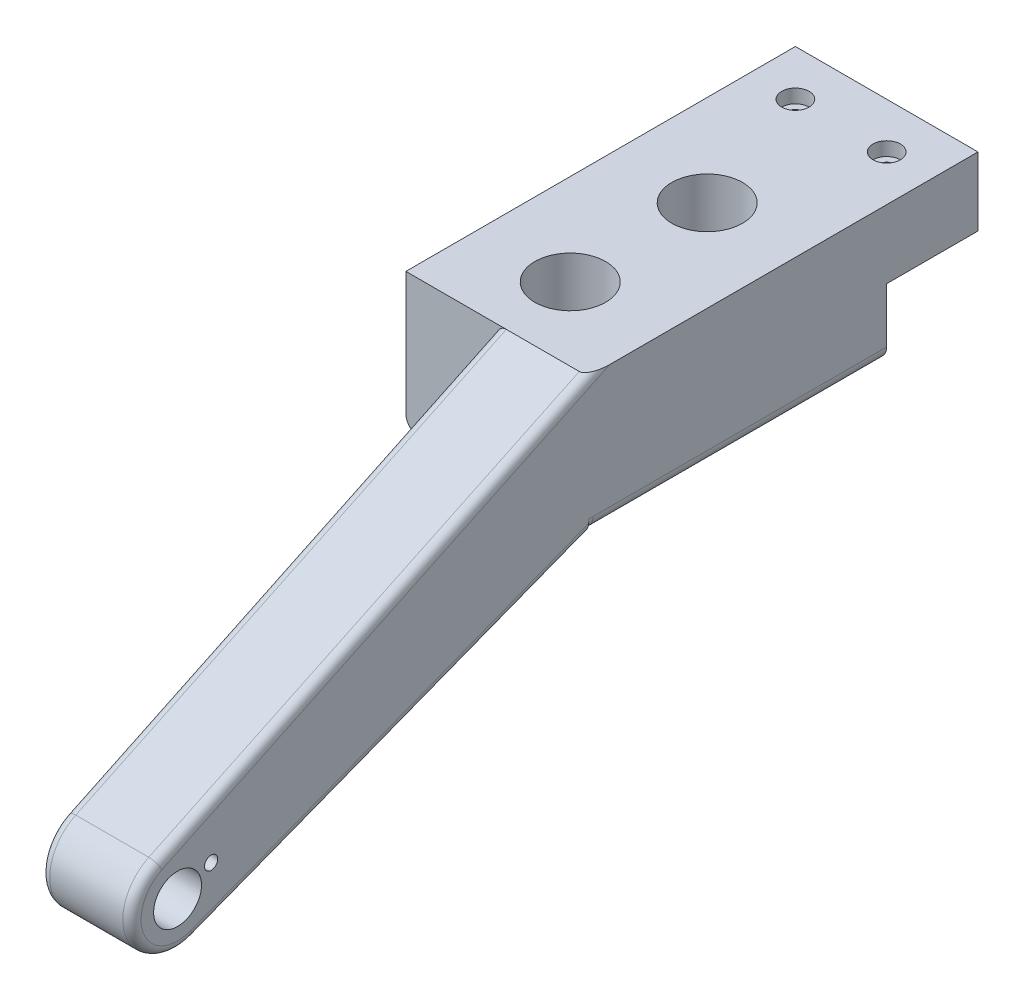
SolidWorks part; units mm, degrees
ref_plane "Front Plane" through (0, 0, 0) normal (0, 0, 1) x (1, 0, 0)
ref_plane "Top Plane" through (0, 0, 0) normal (0, 1, 0) x (1, 0, 0)
ref_plane "Right Plane" through (0, 0, 0) normal (1, 0, 0) x (0, 0, -1)
sketch "Sketch1" plane through (0, 0, 0) normal (0, 1, 0) x (1, 0, 0)
  line L1 (-20, 75) -> (20, 75)
  line L3 (-20, -75) -> (20, -75)
  line L4 (20, -75) -> (20, 75)
  line L5 (-20, -75) -> (-20, 75)
  circle A0 centre (0, -61.1649) radius 7.5
  circle A1 centre (0, -31.1649) radius 7.5
extrude "Boss-Extrude1" add sketch "Sketch1" against normal blind 30 contours L5 L1 L4 L3
sketch "Sketch3" plane through (0, 0, 0) normal (0, 1, 0) x (1, 0, 0)
  circle A0 centre (0, -60) radius 7.5
  circle A1 centre (0, -30) radius 7.5
extrude "Cut-Extrude1" cut sketch "Sketch3" against normal blind 30 contours A0 | A1
sketch "Sketch4" plane through (-20, 0, 0) normal (-1, 0, 0) x (0, 0, 1)
  line L1 (-75, -30) -> (-75, 0) construction
  line L2 (-75, -8) -> (0, -30)
  line L3 (75, -30) -> (-75, -30) construction
  line L4 (0, -30) -> (-75, -30)
  line L5 (-75, -30) -> (-75, -8)
extrude "Cut-Extrude2" cut sketch "Sketch4" against normal blind 49
sketch "Sketch6" plane through (0, 0, -75) normal (0, 0, -1) x (-1, 0, 0)
  line L1 (-20, 0) -> (20, 0)
  line L2 (-20, 0) -> (-20, -30)
  line L3 (-20, -30) -> (20, -30)
  line L4 (20, 0) -> (20, -30)
extrude "Boss-Extrude2" add sketch "Sketch6" along normal blind 50 and the other way blind 87
sketch "Sketch7" plane through (-20, 0, 0) normal (-1, 0, 0) x (0, 0, 1)
  line L1 (-125, -30) -> (-125, 0) construction
  line L2 (-125, -10) -> (-25, -30)
  line L3 (75, -30) -> (-125, -30) construction
  line L4 (-25, -30) -> (-125, -30)
  line L5 (-125, -30) -> (-125, -10)
extrude "Cut-Extrude3" cut sketch "Sketch7" against normal blind 50
sketch "Sketch8" plane through (0, 0, 75) normal (0, 0, 1) x (1, 0, 0)
  line L10 (20, -30) -> (6, -30)
  line L11 (-20, -30) -> (20, -30) construction
  line L12 (6, -30) -> (6, 0)
  line L13 (-20, 0) -> (20, 0) construction
  line L14 (6, 0) -> (20, 0)
  line L15 (20, 0) -> (20, -30)
  line L16 (-20, -30) -> (-6, -30)
  line L17 (-6, -30) -> (-6, 0)
  line L18 (-6, 0) -> (-20, 0)
  line L19 (-20, -30) -> (-20, 0) construction
  line L20 (-20, 0) -> (-20, -30)
extrude "Boss-Extrude4" add sketch "Sketch8" along normal blind 50
sketch "Sketch11" plane through (0, 0, 0) normal (0, 1, 0) x (1, 0, 0)
  line L0 (6, -75) -> (20, -75)
  line L1 (20, -125) -> (20, 125) construction
  line L2 (20, -75) -> (20, -125)
  line L3 (20, -125) -> (6, -125)
  line L4 (6, -125) -> (6, -75)
  line L5 (-6, -75) -> (-6, -125)
  line L6 (-6, -125) -> (-20, -125)
  line L7 (-20, -125) -> (-20, -75)
  line L8 (-20, -125) -> (-20, 125) construction
  line L9 (-20, -75) -> (-6, -75)
extrude "Cut-Extrude4" cut sketch "Sketch11" against normal blind 15
sketch "Sketch12" plane through (0, 0, 125) normal (0, 0, 1) x (1, 0, 0)
  line L1 (-20, -15) -> (-6, -15)
  line L2 (-20, -15) -> (-20, -30)
  line L3 (-20, -30) -> (-6, -30)
  line L4 (-6, -15) -> (-6, -30)
  line L5 (6, -15) -> (20, -15)
  line L6 (6, -15) -> (6, -30)
  line L7 (6, -30) -> (20, -30)
  line L8 (20, -15) -> (20, -30)
extrude "Boss-Extrude5" add sketch "Sketch12" along normal blind 10
sketch "Sketch13" plane through (-6, 0, 0) normal (1, 0, 0) x (0, 0, -1)
  circle A0 centre (-125, -22.5) radius 5
extrude "Boss-Extrude6" add sketch "Sketch13" along normal up to surface (12 mm away) contours A0 up to face at (6, -22.5, 105)
sketch "Sketch14" plane through (0, -30, 0) normal (0, -1, 0) x (1, 0, 0)
  circle A0 centre (0, 60) radius 7.5
  circle A1 centre (0, 60) radius 6
  circle A2 centre (0, 30) radius 6
  circle A3 centre (0, 30) radius 7.5
extrude "Boss-Extrude7" add sketch "Sketch14" against normal blind 5
sketch "Sketch15" plane through (20, 0, 0) normal (1, 0, 0) x (0, 0, -1)
  line L0 (125, 0) -> (105, 0)
  line L1 (-75, 0) -> (125, 0) construction
  circle A0 centre (52.5, 373.9316) radius 377.5991
extrude "Cut-Extrude5" cut sketch "Sketch15" against normal blind 50 contours A0
fillet "Fillet1" radius 3 2 edges at (20, -30, 55) (-20, -30, 55)
fillet "Fillet2" radius 3 8 edges at (-20, -18.5, -82.5) (-19.1213, -29.1213, -29.3934) (0, -30, -25) (19.1213, -29.1213, -29.3934) (-20, -5, -125) (20, -5, -125) (0, -10, -125) (20, -18.5, -82.5)
sketch "Sketch17" plane through (0, 0, 75) normal (0, 0, 1) x (1, 0, 0)
  line L0 (20, 0) -> (20, -30)
  line L1 (14.0365, -30) -> (20, -30)
  line L2 (6, -30) -> (17, -30) construction
  line L3 (20, 0) -> (-20, 0)
  line L4 (-20, 0) -> (-20, -30)
  line L5 (-20, -30) -> (14.0365, -30)
extrude "Boss-Extrude11" add sketch "Sketch17" along normal up to surface (60 mm away) up to face at (13.9243, -23.5243, 135)
sketch "Sketch23" plane through (0, 0, 135) normal (0, 0, 1) x (1, 0, 0)
  line L0 (-20, -15) -> (0, -15)
  line L1 (-20, 0) -> (-20, -30) construction
  line L3 (0, -30) -> (0, -15)
  line L4 (-20, -30) -> (20, -30) construction
  line L6 (-20, -30) -> (0, -30)
  line L7 (-20, -15) -> (-20, -30)
  line L9 (-20, -30) -> (20, -30)
  line L10 (-20, -30) -> (-20, 0)
  line L11 (-20, 0) -> (20, 0)
  line L12 (20, -30) -> (20, 0)
  line M1 (-20, 0) -> (-20, -30)
  line M2 (-20, -30) -> (20, -30)
  line M3 (20, -30) -> (20, 0)
  line M4 (20, 0) -> (-20, 0)
extrude "Cut-Extrude8" cut sketch "Sketch23" against normal up to surface (60 mm away) contours L3 L0 M2 M3 M4 M1 region at (3.3333, -12.5, 135) up to face at (19.2071, -29.2071, 75)
sketch "Sketch25" plane through (0, 0, 75) normal (0, 0, 1) x (1, 0, 0)
  line L0 (-20, -15) -> (-20, 0)
  line L1 (-20, 0) -> (0, 0)
  line L2 (-20, 0) -> (20, 0) construction
  line L3 (0, 0) -> (0, -15)
  line L4 (0, -15) -> (-20, -15)
extrude "Boss-Extrude13" add sketch "Sketch25" along normal up to surface (60 mm away) up to face at (-10, -22.5, 135)
sketch "Sketch26" plane through (0, 0, 0) normal (1, 0, 0) x (0, 0, -1)
  circle A0 centre (-125, -15) radius 5
extrude "Boss-Extrude14" add sketch "Sketch26" along normal up to surface (20 mm away) up to face at (20, -9.3154, -31.9576)
sketch "Sketch27" plane through (0, 0, 75) normal (0, 0, 1) x (1, 0, 0)
  line L1 (20, 0) -> (-20, 0)
  line L2 (20, 0) -> (20, -60)
  line L3 (20, -60) -> (-20, -60)
  line L4 (-20, 0) -> (-20, -60)
extrude "Boss-Extrude15" add sketch "Sketch27" along normal up to surface (60 mm away) up to face at (-10, -15, 135)
sketch "Sketch28" plane through (0, 0, 75) normal (0, 0, -1) x (-1, 0, 0)
  line L0 (20, -27) -> (20, -60) construction
  line L1 (-20, -60) -> (20, -60)
  line L2 (-20, -60) -> (-20, -30)
  line L3 (-20, -30) -> (20, -30)
  line L4 (20, -60) -> (20, -30)
extrude "Cut-Extrude9" cut sketch "Sketch28" against normal blind 1
sketch "Sketch29" plane through (0, 0, 135) normal (0, 0, 1) x (1, 0, 0)
  line L0 (20, 0) -> (-20, 0) construction
  line L1 (20, -60) -> (0, -60)
  line L2 (20, -60) -> (20, 0)
  line L3 (20, 0) -> (0, 0)
  line L4 (0, -60) -> (0, 0)
extrude "Cut-Extrude10" cut sketch "Sketch29" against normal up to surface (59 mm away) up to face at (0, -45, 76)
fillet "Fillet6" radius 3 1 edges at (-20, -30, 75.5)
fillet "Fillet7" radius 3 1 edges at (20, -30, 75.5)
sketch "Sketch30" plane through (0, 0, 135) normal (0, 0, 1) x (1, 0, 0)
  line L0 (-20, 0) -> (-20, -30)
  line L1 (-20, 0) -> (-20, -60) construction
  line L2 (-20, -15) -> (0, -15)
  line L3 (0, 0) -> (0, -60) construction
  line L4 (0, -15) -> (0, 0)
  line L5 (0, 0) -> (-20, 0)
  line M1 (0, -60) -> (0, 0)
  line M2 (0, 0) -> (-20, 0)
  line M3 (-20, 0) -> (-20, -60)
extrude "Cut-Extrude11" cut sketch "Sketch30" against normal up to surface (59 mm away) contours L2 M3 M1 M2 region at (-10, -7.5, 135) up to face at (11.5243, -17.5243, 76)
sketch "Sketch31" plane through (0, 0, 0) normal (1, 0, 0) x (0, 0, -1)
  line L0 (-129.7694, -41.2162) -> (-129.0122, -40.847)
  line L1 (-76, -15) -> (-76, -30)
  line L2 (-76, -30) -> (-118.7075, -57.7744)
  line L3 (-129.6113, -41.0081) -> (-129.7694, -41.2162)
  line L4 (-89.6197, -15) -> (-129.6113, -41.0081)
  line L5 (-76, -30) -> (-76, -60)
  line L6 (-76, -60) -> (-135, -60)
  line L7 (-135, -60) -> (-135, -15)
  line L8 (-135, -15) -> (-76, -15)
  line L9 (-96, -19.1494) -> (-129.6113, -41.0081) construction
  line L10 (-96, -15) -> (-96, -19.1494) construction
  circle A0 centre (-125.0122, -50.0122) radius 10
  line M9 (-76, -15) -> (-135, -15)
  line M10 (-135, -15) -> (-135, -60)
  line M11 (-135, -60) -> (-76, -60)
  line M12 (-76, -60) -> (-76, -30)
  dimension "D1" = 20
extrude "Cut-Extrude13" cut sketch "Sketch31" against normal blind 28 contours A0 M10 M11 | A0 L2 M11 M12 | A0 L3 L4 M9 M10 region at (0, -24.9817, 119.9741) region at (0, -57.7806, 132.7806) region at (0, -50.0084, 91.4032)
sketch "Sketch32" plane through (0, 0, 0) normal (1, 0, 0) x (0, 0, -1)
  line L0 (-76, -30) -> (-76, 0)
  line L1 (-76, 0) -> (-129.7694, -41.2162)
  line L2 (-129.7694, -41.2162) -> (-76, -30)
extrude "Boss-Extrude16" add sketch "Sketch32" against normal up to surface (20 mm away) up to face at (-20, -28.5466, 55.3206)
sketch "Sketch33" plane through (0, 0, 0) normal (1, 0, 0) x (0, 0, -1)
  circle A0 centre (-125.0122, -50.0122) radius 5
extrude "Boss-Extrude17" add sketch "Sketch33" along normal up to surface (20 mm away) contours A0 up to face at (20, -11.526, -18.3379)
ref_plane "Plane2" through (0, 10, 0) normal (0, 1, 0) x (1, 0, 0)
sketch "Sketch34" plane through (0, 0, 0) normal (1, 0, 0) x (0, 0, -1)
  line L0 (-129.6113, -41.0081) -> (-129.7694, -41.2162)
  line L1 (-129.6113, -41.0081) -> (-76, 0)
  line L2 (-76, 0) -> (-76, -30)
  line L3 (-76, -30) -> (-76, 0) construction
  line L4 (-76, -30) -> (-118.7075, -57.7744)
  arc A0 (-129.7694, -41.2162) -> (-118.7075, -57.7744) centre (-125.0122, -50.0122) ccw
extrude "Cut-Extrude15" cut sketch "Sketch34" against normal up to surface (20 mm away) up to face at (-20, -30.8448, 56.4126)
extrude "Cut-Extrude16" cut sketch "Sketch34<2>" along normal up to surface (20 mm away) up to face at (20, -11.526, -18.3379)
sketch "Sketch34<2>" plane through (0, 0, 0) normal (1, 0, 0) x (0, 0, -1) same geometry as "Sketch34"
extrude "Boss-Extrude19" add sketch "Sketch34<3>" along normal up to surface (20 mm away) up to face at (20, -11.526, -18.3379)
sketch "Sketch34<3>" plane through (0, 0, 0) normal (1, 0, 0) x (0, 0, -1) same geometry as "Sketch34"
sketch "Sketch38" plane through (0, 0, 0) normal (-1, 0, 0) x (0, 0, 1)
  circle A0 centre (125.0122, -50.0122) radius 5
sketch "Sketch39" plane through (0, 0, 0) normal (-1, 0, 0) x (0, 0, 1)
  line L0 (162.0273, -59.1835) -> (76, -78.9424)
  line L1 (169.997, -40.8408) -> (76, 0)
  line L2 (76, -30) -> (76, 0) construction
  line L3 (76, 0) -> (129.6113, -41.0081) construction
  line L4 (76, 0) -> (76, -30)
  line L6 (162.0273, -59.1835) -> (76, -30)
  line L7 (76, -78.9424) -> (76, -30)
  arc A0 (162.0273, -59.1835) -> (169.997, -40.8408) centre (166.0122, -50.0122) ccw
  line M6 (129.6113, -41.0081) -> (76, 0)
  line M8 (76, -30) -> (118.7075, -57.7744)
  arc M9 (118.7075, -57.7744) -> (129.7694, -41.2162) centre (125.0122, -50.0122) ccw
  line M10 (129.7694, -41.2162) -> (129.6113, -41.0081)
extrude "Cut-Extrude17" cut sketch "Sketch39" against normal blind 23 contours L7 L0 L6 M9 M8 | L6 M9 M8 region at (0, -58.461, 102.3812) region at (0, -47.5284, 112.7515)
extrude "Boss-Extrude21" add sketch "Sketch39<3>" against normal blind 20 contours L6 A0 L1 M6 M10 M9 region at (0, -36.3816, 138.4753)
sketch "Sketch39<3>" plane through (0, 0, 0) normal (-1, 0, 0) x (0, 0, 1) same geometry as "Sketch39"
sketch "Sketch40" plane through (0, -4.0074, 0) normal (-1, 0, 0) x (0, 0, 1)
  circle A0 centre (166.0122, -50.0122) radius 4.5
extrude "Boss-Extrude22" add sketch "Sketch40" along normal up to surface (12 mm away)
ref_plane "Plane5" through (0, 0, 0) normal (-1, 0, 0) x (0, 0, 1)
sketch "Sketch42" plane through (0, 0, 0) normal (-1, 0, 0) x (0, 0, 1)
  line L0 (166.0122, -54.0196) -> (166.0122, -54.0122)
  line L1 (170.3172, -44.9863) -> (76, 0)
  line L2 (76, 0) -> (76, -30)
  line L3 (162.4124, -63.3418) -> (76, -30)
  line L4 (175.8593, -55.7544) -> (179.2704, -36.4741)
  line L5 (179.2704, -36.4741) -> (76, 0)
  circle A0 centre (166.0122, -54.0122) radius 10
extrude "Cut-Extrude18" cut sketch "Sketch42" against normal blind 20 contours A0 L4 L5 L1 region at (0, -28.5967, 144.6768)
extrude "Boss-Extrude23" add sketch "Sketch42<4>" against normal blind 20 contours A0 L1 L2 L3 | A0 region at (0, -31.8969, 115.5317) region at (0, -48.8269, 174.2302)
sketch "Sketch42<4>" plane through (0, 0, 0) normal (-1, 0, 0) x (0, 0, 1) same geometry as "Sketch42"
sketch "Sketch43" plane through (0, 0, 0) normal (-1, 0, 0) x (0, 0, 1)
  circle A0 centre (166.0122, -54.0196) radius 5.5
fillet "Fillet8" radius 2 6 edges at (20, -46.6709, 119.2062) (20, -57.9675, 175.1967) (0, -46.6709, 119.2062) (0, -57.9675, 175.1967) (20, -22.4932, 123.1586) (0, -22.4932, 123.1586)
sketch "Sketch44" plane through (20, 0, 0) normal (1, 0, 0) x (0, 0, -1)
  line L0 (0, 0) -> (105, 0)
  line L1 (105, 0) -> (105, -4.5055)
  line L2 (105, -4.5055) -> (0, -4.5055)
  line L3 (0, -4.5055) -> (0, 0)
extrude "Boss-Extrude25" add sketch "Sketch44" against normal up to surface (40 mm away) up to face at (-20, -11.526, -18.3379)
sketch "Sketch46" plane through (20, 0, 0) normal (1, 0, 0) x (0, 0, -1)
  line L0 (-71.3543, 0) -> (122, 0) construction
  line L1 (25.3229, 0) -> (-14.6771, 0)
  line L2 (25.3229, 0) -> (25.3229, -6)
  line L3 (25.3229, -27) -> (-14.6771, -27)
  line L4 (-14.6771, 0) -> (-14.6771, -27)
  line L5 (-75, -27) -> (24.7029, -27) construction
  line L6 (63.8734, -19.1659) -> (62.5127, -12.362)
  line L7 (24.7029, -27) -> (122, -7.5406) construction
  line L8 (19.3229, -6) -> (-8.6771, -6)
  line L9 (-8.6771, -6) -> (-8.6771, -21)
  line L10 (19.3229, -21) -> (-8.6771, -21)
  line L12 (19.3229, -21) -> (94.3229, -6)
  line L13 (19.3229, -6) -> (103.4664, -6)
  line L14 (25.3229, -19.8) -> (25.3229, -27)
  line L15 (19.3229, -6) -> (19.3229, -21) construction
  line L16 (25.3229, 0) -> (25.3229, -27) construction
  dimension "D1" = 6
extrude "Cut-Extrude20" cut sketch "Sketch46" against normal blind 59 and the other way through all contours L13 L8 L9 L10 L12 region at (20, -12.0687, -27.6511)
fillet "Fillet10" radius 2 1 edges at (0, -6, -94.3229)
sketch "Sketch48" plane through (0, 0, 8.6771) normal (0, 0, -1) x (-1, 0, 0)
  line L0 (-20, -21) -> (20, -21)
  line L1 (-20, -21) -> (-20, -6)
  line L2 (20, -21) -> (20, -6)
  line L3 (-20, -6) -> (20, -6)
extrude "Boss-Extrude28" add sketch "Sketch48" along normal blind 28
sketch "Sketch49" plane through (20, 0, 0) normal (1, 0, 0) x (0, 0, -1)
  line L0 (19.3229, -6) -> (19.3229, 0)
  line L7 (-71.3543, 0) -> (122, 0) construction
  line L8 (19.3229, -6) -> (19.3229, -30)
  line L9 (19.3229, -30) -> (-20.6771, -30)
  line L10 (-20.6771, -30) -> (-20.6771, 0)
  line L11 (-20.6771, 0) -> (19.3229, 0)
  line L12 (-20.6771, -30) -> (-10.6771, -30)
  line L13 (-10.6771, -30) -> (-10.6771, -15)
  line L14 (-10.6771, -15) -> (9.3229, -15)
  line L15 (9.3229, -15) -> (9.3229, 0)
  line M5 (19.3229, -21) -> (19.3229, -6)
  line M9 (122, 0) -> (-71.3543, 0)
  line M15 (-75, -27) -> (24.7029, -27)
sketch "Sketch50" plane through (0, 0, 0) normal (0, 1, 0) x (1, 0, 0)
  line L0 (20, 9.3229) -> (-20, 9.3229)
  line L1 (-20, -76) -> (-20, 122) construction
  line L2 (-20, 9.3229) -> (-20, -0.6771)
  line L3 (-20, -0.6771) -> (-10, -0.6771)
  line L4 (-10, -0.6771) -> (10, -0.6771)
  circle A0 centre (10, -0.6771) radius 1.5
  circle A1 centre (-10, -0.6771) radius 1.5
extrude "Cut-Extrude21" cut sketch "Sketch49" against normal blind 49 contours L15 L14 L13 L8 L0 M15 M5 M9 | L13 L9 L8 M15 region at (20, -17.0294, -7.264) region at (20, -28.5, -4.3229)
sketch "Sketch51" plane through (0, 0, -19.3229) normal (0, 0, 1) x (1, 0, 0)
  line L1 (24.2973, -37.591) -> (-28.6622, -37.591)
  line L2 (24.2973, -37.591) -> (24.2973, 2.6321)
  line L3 (24.2973, 2.6321) -> (-28.6622, 2.6321)
  line L4 (-28.6622, -37.591) -> (-28.6622, 2.6321)
extrude "Cut-Extrude22" cut sketch "Sketch51" against normal blind 136
extrude "Cut-Extrude23" cut sketch "Sketch50" against normal blind 136 contours A0 | L3 A1 L4 | L4 A1 L3 region at (-10, 0, 0.0405) region at (10, 0, -0.7804) region at (-10, 0, 1.3138)
sketch "Sketch52" plane through (0, 0, 0) normal (0, 1, 0) x (1, 0, 0)
  circle A0 centre (10, -0.6771) radius 3
  circle A1 centre (-10, -0.6771) radius 3
  circle A2 centre (10, -0.6771) radius 1.5
  circle A3 centre (-10, -0.6771) radius 1.5
extrude "Cut-Extrude24" cut sketch "Sketch52" against normal blind 3
sketch "Sketch54" plane through (0, 0, 0) normal (0, 1, 0) x (1, 0, 0)
  circle A0 centre (0, -60) radius 7.75
  circle A1 centre (0, -30) radius 7.75
extrude "Cut-Extrude26" cut sketch "Sketch54" against normal up to surface (25 mm away) up to face at (0, -25, 54)
sketch "Sketch55" plane through (20, 0, 0) normal (1, 0, 0) x (0, 0, -1)
  circle A0 centre (-166.0122, -54.0122) radius 5.25
  circle A2 centre (-158.6646, -50.8479) radius 1.5
extrude "Cut-Extrude27" cut sketch "Sketch55" against normal blind 35 contours A0
sketch "Sketch56" plane through (20, 0, 0) normal (1, 0, 0) x (0, 0, -1)
  circle A1 centre (-158.6646, -50.8479) radius 1.45
extrude "Cut-Extrude28" cut sketch "Sketch56" against normal blind 10
